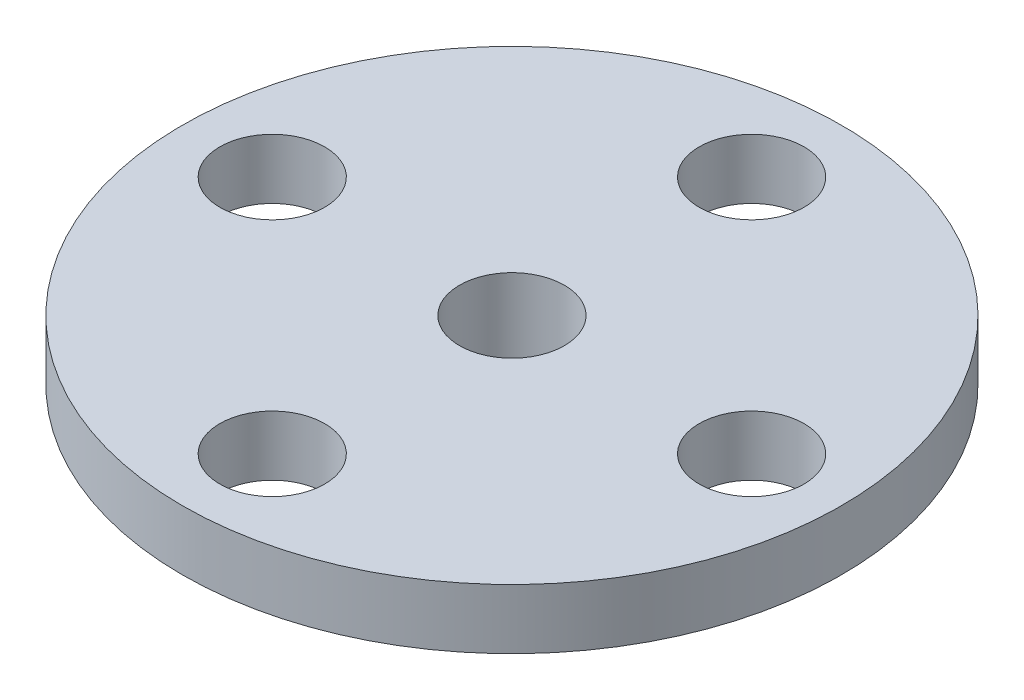
SolidWorks part; units mm, degrees
material "2024 Alloy"
ref_plane "Front Plane" through (0, 0, 0) normal (0, 0, 1) x (1, 0, 0)
ref_plane "Top Plane" through (0, 0, 0) normal (0, 1, 0) x (1, 0, 0)
ref_plane "Right Plane" through (0, 0, 0) normal (1, 0, 0) x (0, 0, -1)
ref_plane "Plane1" through (0, 0, 0) normal (0, 0, -1) x (-1, 0, 0)
sketch "Sketch1" plane through (0, 0, 0) normal (0, 0, -1) x (-1, 0, 0)
  line L0 (-11, 0) -> (0, 0)
  line L1 (0, 0) -> (0, 2)
  line L2 (0, 2) -> (-11, 2)
  line L3 (-11, 2) -> (-11, 0)
  line L4 (0, 0) -> (0, 2) construction
revolve "Revolve1" add sketch "Sketch1" angle 360 about L4 reverse direction yes
sketch "Sketch2" plane through (0, 0, 0) normal (0, -1, 0) x (1, 0, 0)
  circle A0 centre (0, 0) radius 4.4
extrude "Boss-Extrude1" add sketch "Sketch2" along normal blind 4.2
hole_wizard "Ø3.5 (3.5) Diameter Hole1" positions "Sketch4" profile "Sketch3" hole size "Ø3.5" standard "ANSI Metric"
sketch "Sketch4" plane through (0, 0, 0) normal (0, -1, 0) x (-1, 0, 0)
  point P0 (-8, 0)
  point P1 (0, -8)
  point P2 (8, 0)
  point P3 (0, 8)
sketch "Sketch3" plane through (8, 0, 0) normal (1, 0, 0) x (0, 0, -1)
  line L0 (0, 0) -> (0, 2)
  line L1 (0, 2) -> (1.75, 2)
  line L2 (1.75, 2) -> (1.75, 0)
  line L5 (1.75, 0) -> (0, 0)
  line L11 (0, -6.35) -> (0, 107.95) construction
  dimension "Thru Hole Dia." = 3.5
  dimension "Thru Hole Depth" = 2
hole_wizard "CBORE for M3 Hex Head Machine Screw1" positions "Sketch6" profile "Sketch5" counterbore size "M3" standard "ANSI Metric"
sketch "Sketch6" plane through (0, -4.2, 0) normal (0, -1, 0) x (-1, 0, 0)
  point P0 (0, 0)
sketch "Sketch5" plane through (0, -4.2, 0) normal (1, 0, 0) x (0, 0, -1)
  line L0 (0, 0) -> (0, 6.2)
  line L1 (0, 6.2) -> (1.75, 6.2)
  line L3 (1.75, 6.2) -> (1.75, 3)
  line L4 (1.75, 3) -> (2.85, 3)
  line L5 (2.85, 3) -> (2.85, 0)
  line L7 (2.85, 0) -> (0, 0)
  line L11 (0, -6.35) -> (0, 107.95) construction
  dimension "Thru Hole Dia." = 3.5
  dimension "Thru Hole Depth" = 6.2
  dimension "C'Bore Dia." = 5.7
  dimension "C'Bore Depth" = 3
